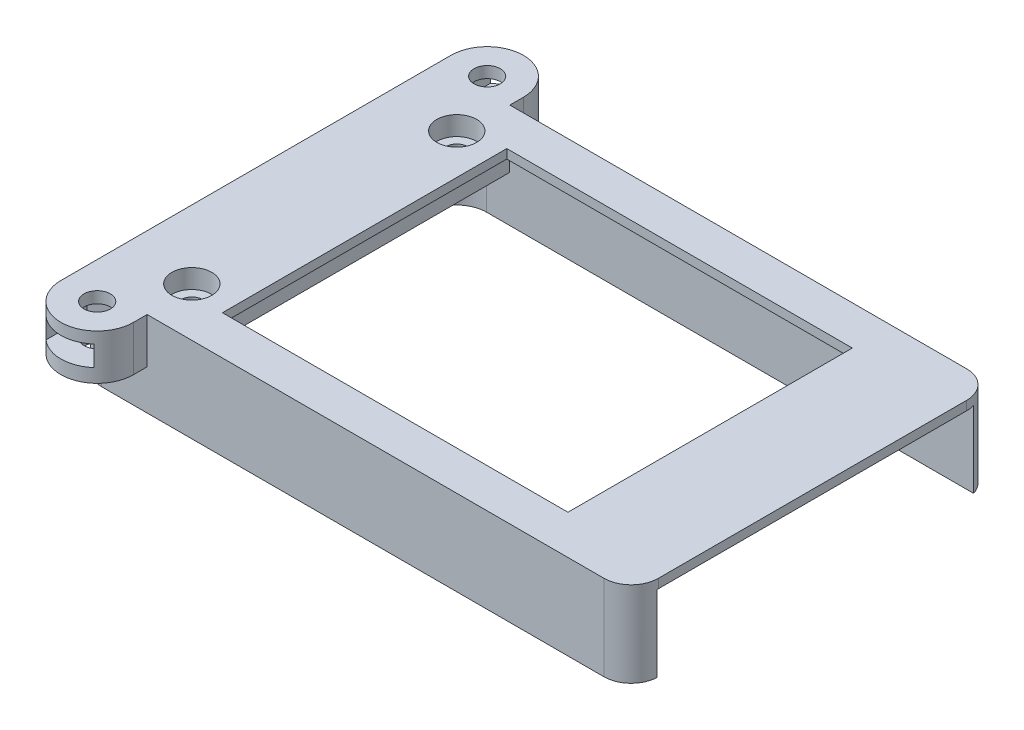
SolidWorks part; units mm, degrees
ref_plane "Front Plane" through (0, 0, 0) normal (0, 0, 1) x (1, 0, 0)
ref_plane "Top Plane" through (0, 0, 0) normal (0, 1, 0) x (1, 0, 0)
ref_plane "Right Plane" through (0, 0, 0) normal (1, 0, 0) x (0, 0, -1)
sketch "Sketch1" plane through (0, 0, 0) normal (0, 0, 1) x (1, 0, 0)
  line L0 (-23.495, -2.8321) -> (-20.447, -2.8321) construction
  line L1 (-20.447, 0) -> (-20.447, -2.8321) construction
  line L2 (-23.495, -2.8321) -> (-26.035, -2.8321) construction
  line L3 (-26.035, -2.8321) -> (-26.035, -4.4196) construction
  line L4 (-23.495, -2.8321) -> (-20.447, -2.8321) construction
  line L5 (-20.447, 0) -> (-20.447, -2.8321) construction
  line L6 (-23.495, -2.8321) -> (-26.035, -2.8321) construction
  line L7 (-26.035, -2.8321) -> (-26.035, -4.4196) construction
  line L8 (-9.4742, -6.2992) -> (-26.035, -6.2992) construction
  line L9 (-26.035, -6.2992) -> (-26.035, -4.4196) construction
  line L10 (-9.4742, -6.2992) -> (-26.035, -6.2992) construction
  line L11 (-26.035, -6.2992) -> (-26.035, -4.4196) construction
  line L12 (-20.947, 1.5) -> (-20.947, -2.8321)
  line L13 (-20.947, -2.8321) -> (-26.035, -2.8321)
  line L14 (-26.035, -2.8321) -> (-26.035, -7.9085)
  line L15 (-28.6272, -8.4085) -> (-21.9464, -8.4085) construction
  line L16 (-28.6272, -8.4085) -> (-21.9464, -8.4085) construction
  line L17 (-26.035, -7.9085) -> (-31.035, -7.9085)
  line L18 (-31.035, -7.9085) -> (-31.035, 1.5)
  line L19 (-31.035, 1.5) -> (-20.947, 1.5)
  line L20 (-20.447, 0) -> (26.0604, 0) construction
  line L21 (-20.447, 0) -> (26.0604, 0) construction
  dimension "D1" = 1
  dimension "D2" = 0.5
  dimension "D3" = 1.5
  dimension "D4" = 5
extrude "Boss-Extrude1" add sketch "Sketch1" along normal mid plane 40
sketch "Sketch2" plane through (0, 1.5, 0) normal (0, 1, 0) x (1, 0, 0)
  line L0 (-24.6493, -17.145) -> (-20.947, -17.145)
  line L1 (-20.947, -20) -> (-20.947, 20) construction
  line L2 (-20.947, -17.145) -> (-20.947, -20)
  line L3 (-20.947, -20) -> (-26.035, -20)
  line L4 (-20.947, -20) -> (-31.035, -20) construction
  line L5 (-26.035, -20) -> (-26.035, -17.145)
  line L6 (-26.035, -20) -> (-26.035, 20) construction
  line L7 (-26.035, -17.145) -> (-26.035, -15.7593)
  line L8 (-23.495, 17.895) -> (-23.495, 20)
  line L9 (-20.947, 20) -> (-31.035, 20) construction
  line L10 (-23.495, 20) -> (-26.035, 20)
  line L11 (-26.035, 20) -> (-26.035, 16.6961)
  arc A0 (-26.035, -14.605) -> (-23.495, -17.145) centre (-23.495, -14.605) ccw construction
  arc A1 (-26.035, -14.605) -> (-23.495, -17.145) centre (-23.495, -14.605) ccw construction
  arc A2 (-23.495, 17.145) -> (-26.035, 14.605) centre (-23.495, 14.605) ccw construction
  arc A3 (-23.495, 17.145) -> (-26.035, 14.605) centre (-23.495, 14.605) ccw construction
  arc A4 (-26.035, -15.7593) -> (-24.6493, -17.145) centre (-23.495, -14.605) ccw
  arc A5 (-26.285, -14.605) -> (-23.495, -17.395) centre (-23.495, -14.605) ccw construction
  arc A6 (-23.495, 17.895) -> (-26.035, 16.6961) centre (-23.495, 14.605) ccw
  arc A7 (-23.495, 17.895) -> (-26.785, 14.605) centre (-23.495, 14.605) ccw construction
  dimension "D1" = 0.25
  dimension "D2" = 0.75
extrude "Boss-Extrude2" add sketch "Sketch2" against normal up to surface (9.4085 mm away) up to face at (-28.535, -7.9085, 0)
fillet "Fillet1" radius 3 2 edges at (-31.035, -3.2043, -20) (-31.035, -3.2043, 20)
sketch "Sketch5" plane through (0, 1.5, 0) normal (0, 1, 0) x (1, 0, 0)
  line L0 (-20.947, 20) -> (27.345, 20)
  line L1 (-20.947, -20) -> (27.345, -20)
  line L2 (30.345, -17) -> (30.345, 17)
  line L3 (-20.947, -20) -> (-20.947, 20) construction
  line L4 (-20.947, -20) -> (-20.947, 20)
  line L5 (29.845, -14.605) -> (29.845, 14.605) construction
  line L8 (19.05, 15.6782) -> (19.05, -15.6781) construction
  line L9 (19.05, -15.6781) -> (-19.05, -15.6782) construction
  line L10 (19.05, 15.6782) -> (-19.05, 15.6781) construction
  line L11 (-19.05, 15.6781) -> (-19.05, -15.6782) construction
  line L12 (19.05, 15.6782) -> (19.05, -15.6781)
  line L13 (19.05, -15.6781) -> (-19.05, -15.6782)
  line L14 (19.05, 15.6782) -> (-19.05, 15.6781)
  line L15 (-19.05, 15.6781) -> (-19.05, -15.6782)
  arc A0 (27.345, -20) -> (30.345, -17) centre (27.345, -17) ccw
  arc A1 (30.345, 17) -> (27.345, 20) centre (27.345, 17) ccw
  arc A2 (-31.035, -17) -> (-28.035, -20) centre (-28.035, -17) ccw construction
  dimension "D1" = 0.5
extrude "Boss-Extrude5" add sketch "Sketch5" against normal offset from surface (1 mm away) 0.5
sketch "Sketch6" plane through (0, 0.5, 0) normal (0, -1, 0) x (1, 0, 0)
  line L0 (-23.495, 17.145) -> (27.305, 17.145) construction
  line L1 (-20.947, 17.145) -> (26.8104, 17.145)
  line L2 (26.0604, -17.145) -> (-20.447, -17.145) construction
  line L3 (-20.947, 20) -> (-20.947, -20) construction
  line L4 (-20.947, 20) -> (-20.947, 17.145)
  line L5 (27.345, 20) -> (-20.947, 20) construction
  line L6 (27.345, 20) -> (-20.947, 20)
  line L7 (-20.947, -20) -> (27.345, -20) construction
  line L8 (30.345, -17) -> (30.345, 17) construction
  line L9 (-20.947, -20) -> (27.345, -20)
  line L10 (30.345, -17) -> (30.345, 17)
  line L11 (26.0604, 17.145) -> (26.0604, 14.4018) construction
  line L12 (26.0604, 17.145) -> (26.0604, 14.4018) construction
  line L13 (26.8104, 17.145) -> (26.8104, -17.895)
  line L14 (26.0604, -17.145) -> (-20.447, -17.145) construction
  line L15 (-20.947, -20) -> (-20.947, -17.895)
  line L16 (-20.947, -17.895) -> (26.8104, -17.895)
  arc A4 (30.345, 17) -> (27.345, 20) centre (27.345, 17) ccw construction
  arc A5 (30.345, 17) -> (27.345, 20) centre (27.345, 17) ccw
  arc A6 (27.345, -20) -> (30.345, -17) centre (27.345, -17) ccw construction
  arc A7 (27.345, -20) -> (30.345, -17) centre (27.345, -17) ccw
  dimension "D2" = 1.5
extrude "Boss-Extrude6" add sketch "Sketch6" along normal up to surface (3.3321 mm away)
sketch "Sketch7" plane through (0, -2.8321, 0) normal (0, -1, 0) x (1, 0, 0)
  line L1 (-20.947, 20) -> (27.345, 20)
  line L2 (-20.947, 20) -> (-20.947, 17.145)
  line L3 (-20.947, 17.145) -> (30.3415, 17.145)
  line L6 (-23.495, -20) -> (27.345, -20)
  line L7 (-23.495, -20) -> (-23.495, -17.895)
  line L8 (-23.495, -17.895) -> (30.2084, -17.895)
  arc A0 (30.345, 17) -> (27.345, 20) centre (27.345, 17) ccw construction
  arc A1 (27.345, -20) -> (30.345, -17) centre (27.345, -17) ccw construction
  arc A2 (30.3415, 17.145) -> (27.345, 20) centre (27.345, 17) ccw
  arc A3 (27.345, -20) -> (30.2084, -17.895) centre (27.345, -17) ccw
extrude "Boss-Extrude7" add sketch "Sketch7" along normal up to surface (5.0764 mm away) up to face at (-25.9315, -7.9085, 1.3908)
sketch "Sketch9" plane through (0, 1.5, 0) normal (0, 1, 0) x (1, 0, 0)
  line L0 (-31.035, 17) -> (-31.035, 21.5)
  line L1 (-23.035, 21.5) -> (-23.035, 20)
  line L2 (27.345, 20) -> (-28.035, 20) construction
  line L3 (-23.035, 20) -> (-28.035, 20)
  line L4 (0, 0) -> (-7.0217, 0) construction
  line L5 (-23.035, -20) -> (-28.035, -20)
  line L6 (-23.035, -21.5) -> (-23.035, -20)
  line L7 (-31.035, -17) -> (-31.035, -21.5)
  arc A0 (-31.035, 21.5) -> (-23.035, 21.5) centre (-27.035, 21.5) cw
  arc A1 (-28.035, 20) -> (-31.035, 17) centre (-28.035, 17) ccw
  arc A2 (-28.035, -20) -> (-31.035, -17) centre (-28.035, -17) cw
  arc A3 (-31.035, -21.5) -> (-23.035, -21.5) centre (-27.035, -21.5) ccw
  dimension "D1" = 8
  dimension "D2" = 1.5
extrude "Boss-Extrude8" add sketch "Sketch9" against normal blind 5
hole_wizard "M2.5 Clearance Hole1" positions "Sketch10" profile "Sketch11" hole size "M2.5" standard "ANSI Metric" end condition through all
sketch "Sketch10" plane through (0, 1.5, 0) normal (0, 1, 0) x (1, 0, 0)
  point P0 (-27.035, -21.5)
  point P3 (-27.035, 21.5)
sketch "Sketch11" plane through (-27.035, 1.5, 21.5) normal (1, 0, 0) x (0, 0, 1)
  line L0 (0, 0) -> (0, 9.4085)
  line L1 (0, 9.4085) -> (1.45, 9.4085)
  line L2 (1.45, 9.4085) -> (1.45, 0)
  line L5 (1.45, 0) -> (0, 0)
  line L11 (0, -6.35) -> (0, 107.95) construction
  dimension "Thru Hole Dia." = 2.9
  dimension "Thru Hole Depth" = 9.4085
ref_plane "Plane1" through (0, -2, 0) normal (0, 1, 0) x (1, 0, 0)
sketch "Sketch12" plane through (0, -2, 0) normal (0, 1, 0) x (1, 0, 0)
  line L0 (-29.685, -23.03) -> (-29.685, -29.56)
  line L1 (-24.385, -23.03) -> (-24.385, -19.97)
  line L2 (-24.385, -19.97) -> (-27.035, -18.44)
  line L3 (-27.035, -18.44) -> (-29.685, -19.97)
  line L4 (-29.685, -19.97) -> (-29.685, -23.03)
  line L5 (-29.685, -23.03) -> (-27.035, -24.56) construction
  line L6 (-27.035, -24.56) -> (-24.385, -23.03) construction
  line L13 (-29.685, -29.56) -> (-24.385, -29.56)
  line L14 (-24.385, -29.56) -> (-24.385, -23.03)
  line L15 (0, 0) -> (-12.2155, 0) construction
  line L16 (-29.685, 23.03) -> (-29.685, 29.56)
  line L17 (-29.685, 29.56) -> (-24.385, 29.56)
  line L18 (-24.385, 29.56) -> (-24.385, 23.03)
  line L19 (-24.385, 23.03) -> (-24.385, 19.97)
  line L20 (-24.385, 19.97) -> (-27.035, 18.44)
  line L21 (-27.035, 18.44) -> (-29.685, 19.97)
  line L22 (-29.685, 19.97) -> (-29.685, 23.03)
  circle A0 centre (-27.035, -21.5) radius 2.65 construction
  circle A2 centre (-27.035, -21.5) radius 2.5 construction
  dimension "D1" = 5
  dimension "D2" = 0.15
  dimension "D3" = 5
extrude "Cut-Extrude1" cut sketch "Sketch12" along normal blind 2.25
sketch "Sketch13" plane through (0, 1.5, 0) normal (0, 1, 0) x (1, 0, 0)
  circle A0 centre (-23.495, 14.605) radius 1.016 construction
  circle A1 centre (-23.495, -14.605) radius 1.016 construction
  circle A2 centre (27.305, -14.605) radius 1.016 construction
  circle A3 centre (27.305, 14.605) radius 1.016 construction
  circle A4 centre (-23.495, 14.605) radius 1.016
  circle A5 centre (-23.495, -14.605) radius 1.016
  circle A6 centre (27.305, -14.605) radius 1.016
  circle A7 centre (27.305, 14.605) radius 1.016
hole_wizard "CBORE for M2 SHCS1" positions "Sketch14" profile "Sketch15" counterbore size "M2" standard "ANSI Metric" end condition through all
sketch "Sketch14" plane through (0, 1.5, 0) normal (0, 1, 0) x (1, 0, 0)
  point P0 (-23.495, -14.605)
  point P3 (-23.495, 14.605)
sketch "Sketch15" plane through (-23.495, 1.5, 14.605) normal (1, 0, 0) x (0, 0, 1)
  line L0 (0, 0) -> (0, 9.4085)
  line L1 (0, 9.4085) -> (1.2, 9.4085)
  line L3 (1.2, 9.4085) -> (1.2, 2.1)
  line L4 (1.2, 2.1) -> (2.2, 2.1)
  line L5 (2.2, 2.1) -> (2.2, 0)
  line L7 (2.2, 0) -> (0, 0)
  line L11 (0, -6.35) -> (0, 107.95) construction
  dimension "Thru Hole Dia." = 2.4
  dimension "Thru Hole Depth" = 9.4085
  dimension "C'Bore Dia." = 4.4
  dimension "C'Bore Depth" = 2.1
sketch "Sketch16" plane through (26.8104, 0, 0) normal (-1, 0, 0) x (0, 0, 1)
  line L4 (-17.895, 0.5) -> (-17.895, -2.8321)
  line L5 (-17.895, -2.8321) -> (17.145, -2.8321)
  line L6 (17.145, -2.8321) -> (17.145, 0.5)
  line L7 (17.145, 0.5) -> (-17.895, 0.5)
  line L8 (-17.895, 0.5) -> (-17.895, -2.8321)
  line L9 (-17.895, -2.8321) -> (17.145, -2.8321)
  line L10 (17.145, -2.8321) -> (17.145, 0.5)
  line L11 (17.145, 0.5) -> (-17.895, 0.5)
  dimension "D1" = 0
extrude "Cut-Extrude2" cut sketch "Sketch16" against normal through all
